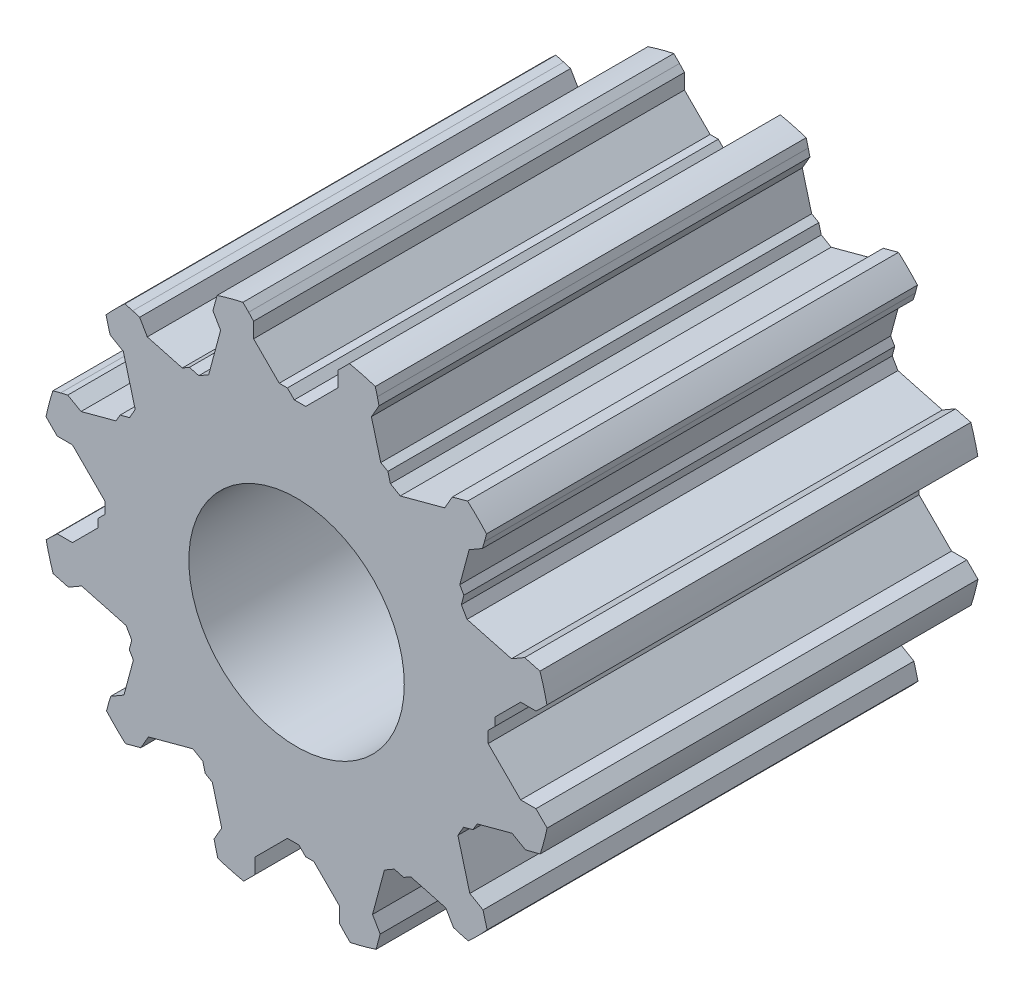
SolidWorks part; units mm, degrees
ref_plane "Front Plane" through (0, 0, 0) normal (0, 0, 1) x (1, 0, 0)
ref_plane "Top Plane" through (0, 0, 0) normal (0, 1, 0) x (1, 0, 0)
ref_plane "Right Plane" through (0, 0, 0) normal (1, 0, 0) x (0, 0, -1)
sketch "Sketch1" plane through (0, 0, 0) normal (0, 0, 1) x (1, 0, 0)
  circle A0 centre (0, 0) radius 3.5657
  circle A1 centre (0, 0) radius 1.5
extrude "Boss-Extrude1" add sketch "Sketch1" along normal blind 6
sketch "Sketch2" plane through (0, 0, 0) normal (0, 0, 1) x (1, 0, 0)
  line L0 (3.9637, 0.7472) -> (3.4866, 0.7472)
  line L1 (3.4866, 0.7472) -> (3.4068, 0.6675)
  line L2 (3.4068, 0.6675) -> (3.3331, 0.5983)
  line L3 (3.3331, 0.5983) -> (3.2252, 0.5983)
  line L4 (3.2252, 0.5983) -> (3.1206, 0.5983)
  line L5 (3.1206, 0.5983) -> (3.0234, 0.5011)
  line L6 (3.0234, 0.5011) -> (2.9489, 0.4266)
  line L7 (2.9489, 0.4266) -> (2.8536, 0.3313)
  line L8 (2.8536, 0.3313) -> (2.7635, 0.2413)
  line L9 (2.7635, 0.2413) -> (2.7635, 0.1273)
  line L10 (2.7635, 0.1273) -> (2.6677, 0.0315)
  line L11 (2.6677, 0.0315) -> (2.6677, -0.1273)
  line L12 (2.6677, -0.1273) -> (2.7635, -0.2231)
  line L13 (2.7635, -0.2231) -> (2.8536, -0.3131)
  line L14 (2.8536, -0.3131) -> (2.9489, -0.4084)
  line L15 (2.9489, -0.4084) -> (3.0234, -0.4829)
  line L16 (3.0234, -0.4829) -> (3.1206, -0.5801)
  line L17 (3.1206, -0.5801) -> (3.2252, -0.5801)
  line L18 (3.2252, -0.5801) -> (3.3331, -0.5801)
  line L19 (3.3331, -0.5801) -> (3.4068, -0.6538)
  line L20 (3.4068, -0.6538) -> (3.4889, -0.7359)
  line L21 (3.4889, -0.7359) -> (3.9637, -0.7359)
  line L22 (3.9637, -0.7359) -> (3.9637, 0.7472)
  circle A0 centre (0, 0) radius 3.5657 construction
extrude "Cut-Extrude2" cut sketch "Sketch2" along normal blind 6.2
ref_axis "Axis1" through (0, 0, -0.3) along (0, 0, 1)
pattern_circular "CirPattern1" count 12 every 30 about axis through (0, 0, -0.3) along (0, 0, 1) of "Cut-Extrude2"
